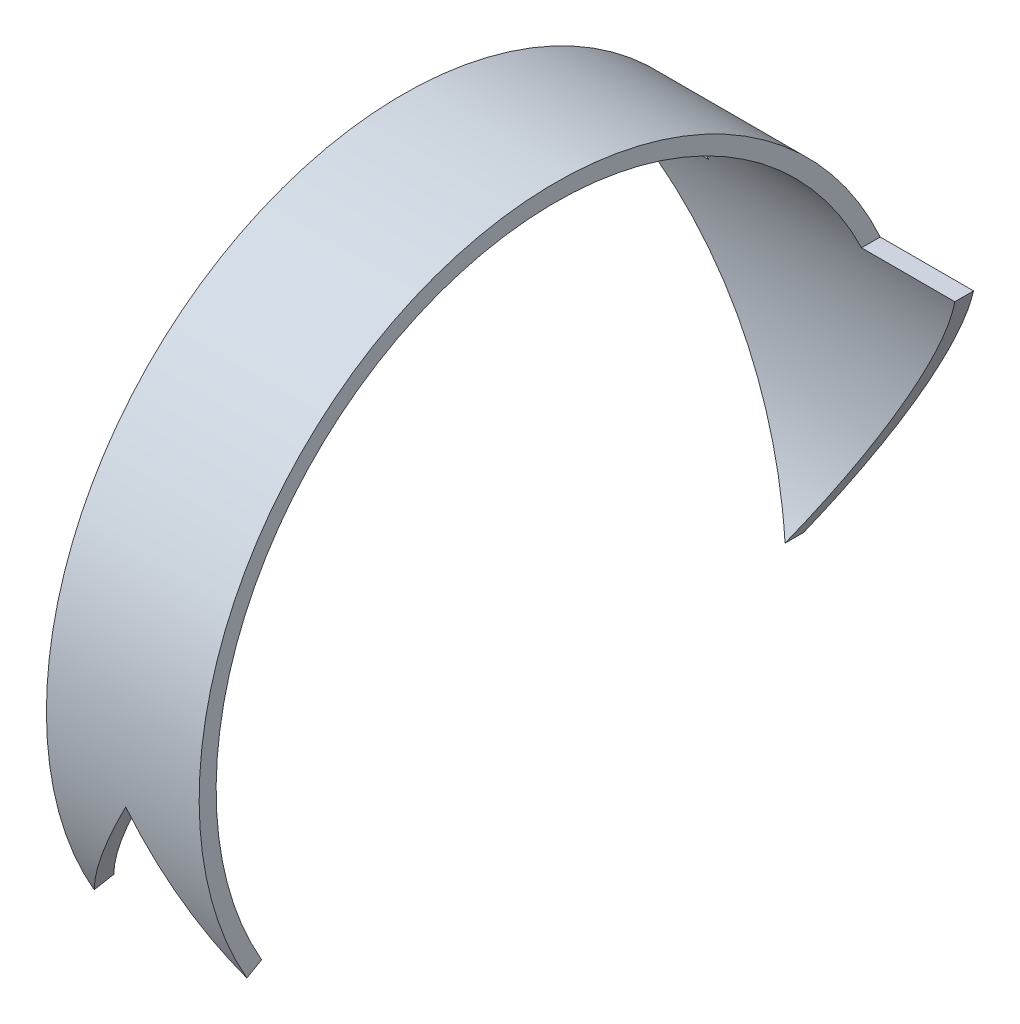
SolidWorks part; units mm, degrees
note: '?' marks a value the reader was unsure of.
ref_plane "SketchPlanes" through (0, 0, 0) normal (0, 0, 1) x (1, 0, 0)
ref_plane "Plane2" through (0, 0, 0) normal (0, 1, 0) x (1, 0, 0)
ref_plane "Symmetry" through (0, 0, 0) normal (1, 0, 0) x (0, 0, -1)
sketch "circularband" plane through (0, 0, 0) normal (0, 0, 1) x (1, 0, 0)
  line L0 (-7.5, 15.75) -> (7.5, 15.75)
  line L1 (-7.5, 15.75) -> (-7.5, 15)
  line L2 (7.5, 15) -> (-7.5, 15)
  line L3 (7.5, 15) -> (7.5, 15.75)
  line L4 (0, 0) -> (9.9102, 0) construction
  point P4 (0, 15)
  dimension "headwidth" = 15
  dimension "radius" = 15
  dimension "thickness" = 0.75
revolve "Base-Revolve" add sketch "circularband" angle 120 about L4
ref_axis "arrowaxis" through (-50, 0, 0) along (1, 0, 0)?
sketch "arrowpattern" plane through (0, 0, 0) normal (0, 0, 1) x (1, 0, 0)
  line L0 (-7.5, 6.4904) -> (7.5, 6.4904) construction
  line L1 (-7.5, 6.4904) -> (0, -6.5) construction
  line L2 (0, -6.5) -> (7.5, 6.4904) construction
  line L3 (-3.375, -7.875) -> (-3.375, 13.125) construction
  line L4 (3.375, -7.875) -> (3.375, 13.125) construction
  line L5 (-7.5, 15.75) -> (-7.5, -7.875) construction
  line L6 (-3.375, -7.875) -> (0, -2.0293) construction
  line L7 (0, -2.0293) -> (3.375, -7.875) construction
  line L8 (-3.375, 13.125) -> (3.375, 13.125) construction
  line L9 (7.5, -7.875) -> (7.5, 15.75) construction
  line L10 (7.5, -7.5) -> (-7.5, -7.5) construction
  line L13 (-7.5, -7.875) -> (7.5, -7.875) construction
  point P11 (0, -7.5)
  dimension "D1" = 1
  dimension "headangle" = 60
  dimension "tailwidth" = 6.75
sketch "Sketch13" plane through (0, 0, 0) normal (0, 1, 0) x (1, 0, 0)
  line L0 (0, 12.9904) -> (-7.5, 0) construction
  line L1 (-7.5, 0) -> (7.5, 0) construction
  line L2 (-3.375, 0) -> (-3.375, -12.9904) construction
  line L3 (-3.375, -12.9904) -> (0, -7.1447) construction
  line L4 (0, -7.1447) -> (3.375, -12.9904) construction
  line L5 (3.375, -12.9904) -> (3.375, 0) construction
  line L6 (0, 15.75) -> (0, 12.9904) construction
  line L7 (7.5, 0) -> (0, 12.9904) construction
  line L8 (-3.375, -12.9904) -> (3.375, -12.9904) construction
  line L9 (-7.5, 0) -> (0, 12.9904)
  line L10 (7.5, 12.9904) -> (-7.5, 12.9904) construction
  line L11 (7.5, -12.9904) -> (-7.5, -12.9904) construction
  line L12 (7.5, 15.75) -> (-7.5, 15.75) construction
  line L14 (0, -7.1447) -> (0, -15.75) construction
  line L15 (-7.5, -15.75) -> (7.5, -15.75) construction
  line L16 (0, 12.9904) -> (-7.5, 0) construction
  line L17 (-7.5, 0) -> (7.5, 0) construction
  line L18 (7.5, 0) -> (0, 12.9904) construction
  line L19 (-3.375, 0) -> (-3.375, -12.9904) construction
  line L20 (-3.375, -12.9904) -> (0, -7.1447) construction
  line L21 (0, -7.1447) -> (3.375, -12.9904) construction
  line L22 (3.375, -12.9904) -> (3.375, 0) construction
  line L23 (0, 12.9904) -> (7.5, 0)
  line L24 (7.5, 0) -> (3.375, 0)
  line L25 (3.375, 0) -> (3.375, -12.9904)
  line L26 (3.375, -12.9904) -> (0, -7.1447)
  line L27 (0, -7.1447) -> (-3.375, -12.9904)
  line L28 (-3.375, -12.9904) -> (-3.375, 0)
  line L29 (-3.375, 0) -> (-7.5, 0)
  line L30 (-12.639, -4.3301) -> (-12.639, 4.3301) construction
  line L31 (-12.639, -4.3301) -> (-12.639, -12.9904) construction
  line L32 (-12.639, 4.3301) -> (-12.639, 12.9904) construction
  point P21 (-12.639, 0)
sketch "Sketch9" plane through (0, 0, 0) normal (0, 0, 1) x (1, 0, 0)
  line L0 (-3.375, 15.75) -> (3.375, 15.75)
  line L1 (3.375, 15.75) -> (3.375, 6.4904)
  line L2 (-7.5, 6.4904) -> (7.5, 6.4904) construction
  line L3 (3.375, 6.4904) -> (7.5, 6.4904)
  line L4 (7.5, 6.4904) -> (0, -6.5)
  line L5 (0, -6.5) -> (-7.5, 6.4904)
  line L6 (-7.5, 6.4904) -> (-3.375, 6.4904)
  line L7 (-3.375, 6.4904) -> (-3.375, 15.75)
  line L8 (-7.5, 15.75) -> (7.5, 15.75) construction
  line L9 (0, 15) -> (0, 15.75) construction
  line L10 (-3.375, -7.875) -> (-3.375, 13.125) construction
extrude "head1" cut sketch "Sketch9" against normal through all flip side to cut
sketch "Sketch10" plane through (0, 0, 0) normal (0, 0, 1) x (1, 0, 0)
  line L0 (-7.5, 15.75) -> (7.5, 15.75) construction
  line L1 (0, -2.0293) -> (3.375, -7.875)
  line L2 (3.375, -7.875) -> (3.375, 15.75)
  line L3 (3.375, 15.75) -> (-3.375, 15.75)
  line L4 (-3.375, 15.75) -> (-3.375, -7.875)
  line L5 (0, -2.0293) -> (-3.375, -7.875)
  line L6 (0, 15) -> (0, 15.75) construction
extrude "tail1" cut sketch "Sketch10" along normal through all flip side to cut
sketch "Sketch11" plane through (0, 0, 0) normal (0, 0, 1) x (1, 0, 0)
  line L0 (-3.375, 13.125) -> (3.375, 13.125)
  line L1 (3.375, 13.125) -> (3.375, 6.4904)
  line L2 (-7.5, 6.4904) -> (7.5, 6.4904) construction
  line L3 (3.375, 6.4904) -> (7.5, 6.4904)
  line L4 (7.5, 6.4904) -> (0, -6.5)
  line L5 (0, -6.5) -> (-7.5, 6.4904)
  line L6 (-7.5, 6.4904) -> (-3.375, 6.4904)
  line L7 (-3.375, 6.4904) -> (-3.375, 13.125)
extrude "head2" [suppressed] cut sketch "Sketch11" along normal through all flip side to cut
sketch "Sketch12" plane through (0, 0, 0) normal (0, 0, 1) x (1, 0, 0)
  line L0 (-3.375, 13.125) -> (3.375, 13.125)
  line L1 (3.375, 13.125) -> (3.375, -7.875)
  line L2 (3.375, -7.875) -> (0, -2.0293)
  line L3 (0, -2.0293) -> (-3.375, -7.875)
  line L4 (-3.375, -7.875) -> (-3.375, 13.125)
extrude "tail2" [suppressed] cut sketch "Sketch12" against normal through all flip side to cut
extrude "Cut-Extrude1" [suppressed] cut sketch "Sketch13" against normal through all and the other way through all flip side to cut
